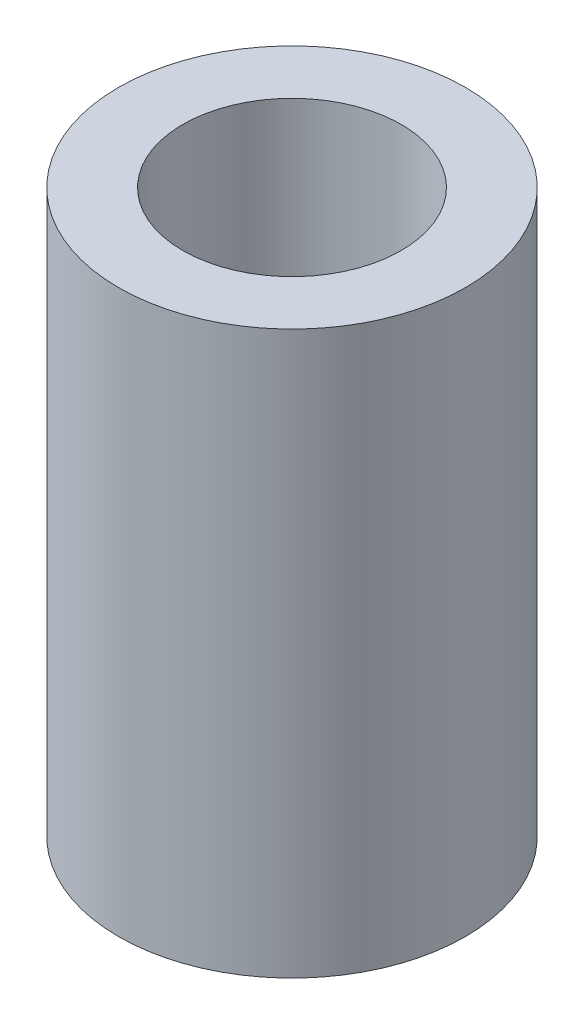
SolidWorks part; units mm, degrees
ref_plane "Front Plane" through (0, 0, 0) normal (0, 0, 1) x (1, 0, 0)
ref_plane "Top Plane" through (0, 0, 0) normal (0, 1, 0) x (1, 0, 0)
ref_plane "Right Plane" through (0, 0, 0) normal (1, 0, 0) x (0, 0, -1)
sketch "Sketch1" plane through (0, 0, 0) normal (0, 1, 0) x (1, 0, 0)
  circle A0 centre (0, 0) radius 6.35
  dimension "D1" = 12.7
extrude "Boss-Extrude1" add sketch "Sketch1" along normal blind 20.58
sketch "Sketch2" plane through (0, 20.58, 0) normal (0, 1, 0) x (1, 0, 0)
  circle A0 centre (0, 0) radius 4
  dimension "D1" = 8
sketch "Sketch3" plane through (0, 20.58, 0) normal (0, 1, 0) x (1, 0, 0)
  circle A0 centre (0, 0) radius 4
  dimension "D1" = 8
extrude "Cut-Extrude2" cut sketch "Sketch3" against normal through all
